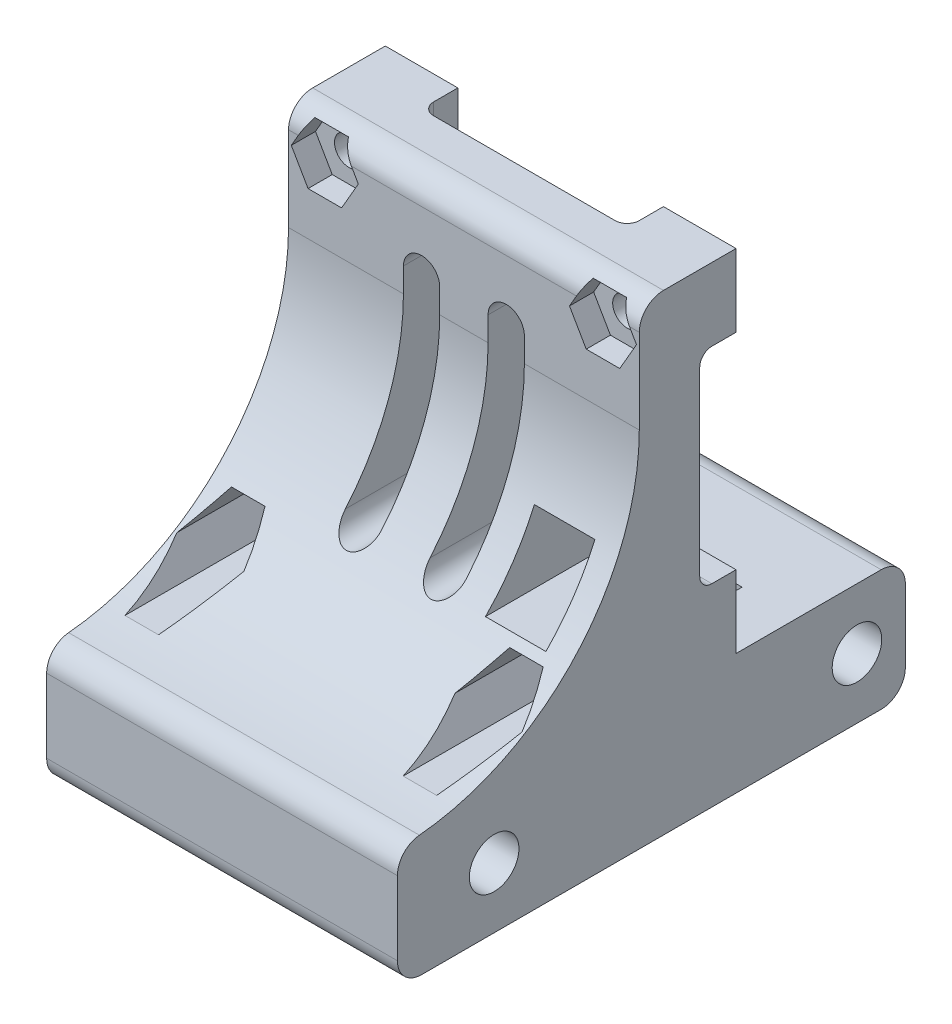
SolidWorks part; units mm, degrees
ref_plane "Front Plane" through (0, 0, 0) normal (0, 0, 1) x (1, 0, 0)
ref_plane "Top Plane" through (0, 0, 0) normal (0, 1, 0) x (1, 0, 0)
ref_plane "Right Plane" through (0, 0, 0) normal (1, 0, 0) x (0, 0, -1)
sketch "Sketch3" plane through (0, 0, 0) normal (0, 0, 1) x (1, 0, 0)
  line L0 (14.5, 29) -> (14.5, 0) construction
  line L1 (0, 0) -> (29, 0)
  line L2 (0, 0) -> (0, 29)
  line L3 (0, 29) -> (29, 29)
  line L4 (29, 0) -> (29, 29)
  line L5 (0, 14.5) -> (29, 14.5) construction
  line L6 (18, 7) -> (18, 22) construction
  line L7 (27, 12) -> (22, 12)
  line L8 (27, 12) -> (27, 6)
  line L9 (27, 6) -> (22, 6)
  line L10 (22, 12) -> (22, 6)
  line L11 (16.5, 7) -> (16.5, 22)
  line L12 (19.5, 7) -> (19.5, 22)
  line L13 (11, 7) -> (11, 22) construction
  line L14 (12.5, 7) -> (12.5, 22)
  line L15 (9.5, 7) -> (9.5, 22)
  circle A0 centre (3, 26) radius 1.2
  circle A1 centre (26, 26) radius 1.2
  circle A2 centre (26, 3) radius 1.2
  circle A3 centre (3, 3) radius 1.2
  arc A4 (16.5, 7) -> (19.5, 7) centre (18, 7) ccw
  arc A5 (19.5, 22) -> (16.5, 22) centre (18, 22) ccw
  arc A6 (12.5, 7) -> (9.5, 7) centre (11, 7) cw
  arc A7 (9.5, 22) -> (12.5, 22) centre (11, 22) cw
  point P23 (18, 14.5)
  point P31 (11, 14.5)
  dimension "D3" = 2.4
  dimension "D1" = 29
  dimension "D2" = 29
  dimension "D4" = 11.5
  dimension "D5" = 11.5
  dimension "D6" = 2
  dimension "D7" = 6
  dimension "D8" = 6
  dimension "D9" = 5
  dimension "D10" = 15
  dimension "D11" = 3
  dimension "D12" = 3.5
extrude "Boss-Extrude1" add sketch "Sketch3" along normal blind 5
sketch "Sketch4" plane through (0, 0, 0) normal (0, 1, 0) x (1, 0, 0)
  line L0 (29, -5) -> (29, 0) construction
  line L1 (0, 17) -> (29, 17)
  line L2 (0, 17) -> (0, -25)
  line L3 (0, -25) -> (29, -25)
  line L4 (29, 17) -> (29, -25)
  line L5 (0, -5) -> (0, 0) construction
  line L6 (0, -5) -> (29, -5) construction
  line L7 (0, 0) -> (29, 0) construction
  line L8 (24.5, -3) -> (4.5, -3)
  line L9 (24.5, -3) -> (24.5, 8)
  line L10 (24.5, 8) -> (4.5, 8)
  line L11 (4.5, -3) -> (4.5, 8)
  line L12 (14.5, 0) -> (14.5, -6) construction
  point P18 (14.5, -3)
  dimension "D1" = 42
  dimension "D2" = 20
  dimension "D3" = 20
  dimension "D4" = 11
  dimension "D5" = 3
extrude "Boss-Extrude2" add sketch "Sketch4" against normal blind 10 contours L2 L3 L4 L1 | L9 L8 L11 L10
sketch "Sketch5" plane through (0, 0, 0) normal (0, 0, -1) x (-1, 0, 0)
  line L0 (-14.5, 29) -> (-14.5, 14.5) construction
  line L1 (-29, 0) -> (-23, 0)
  line L2 (-29, 0) -> (-29, 6)
  line L3 (-29, 6) -> (-23, 6)
  line L4 (-23, 0) -> (-23, 6)
  line L5 (-29, 29) -> (0, 29) construction
  line L7 (-29, 14.5) -> (0, 14.5) construction
  line L8 (-29, 0) -> (-29, 29) construction
  line L9 (0, 29) -> (0, 0) construction
  line L10 (-29, 23) -> (-23, 23)
  line L11 (-23, 29) -> (-23, 23)
  line L12 (-29, 29) -> (-23, 29)
  line L13 (-29, 29) -> (-29, 23)
  line L14 (0, 6) -> (-6, 6)
  line L15 (-6, 0) -> (-6, 6)
  line L16 (0, 0) -> (-6, 0)
  line L17 (0, 0) -> (0, 6)
  line L18 (0, 29) -> (0, 23)
  line L19 (0, 29) -> (-6, 29)
  line L20 (-6, 29) -> (-6, 23)
  line L21 (0, 23) -> (-6, 23)
  circle A0 centre (-26, 3) radius 1.2 construction
  circle A1 centre (-3, 3) radius 1.2 construction
  circle A2 centre (-3, 26) radius 1.2 construction
  circle A3 centre (-26, 26) radius 1.2 construction
  circle A4 centre (-26, 3) radius 1.2
  circle A5 centre (-3, 3) radius 1.2
  circle A6 centre (-3, 26) radius 1.2
  circle A7 centre (-26, 26) radius 1.2
  dimension "D1" = 6
  dimension "D2" = 6
extrude "Boss-Extrude3" add sketch "Sketch5" along normal blind 3
fillet "Fillet1" radius 20 1 edges at (14.5, 0, 5)
sketch "Sketch6" plane through (0, 0, 5) normal (0, 0, 1) x (1, 0, 0)
  line L1 (4.3856, 0.6) -> (5.7713, 3)
  line L2 (5.7713, 3) -> (4.3856, 5.4)
  line L3 (4.3856, 5.4) -> (1.6144, 5.4)
  line L4 (1.6144, 5.4) -> (0.2287, 3)
  line L5 (0.2287, 3) -> (1.6144, 0.6)
  line L6 (1.6144, 0.6) -> (4.3856, 0.6)
  line L7 (24.6144, 0.6) -> (27.3856, 0.6)
  line L8 (27.3856, 0.6) -> (28.7713, 3)
  line L9 (28.7713, 3) -> (27.3856, 5.4)
  line L10 (27.3856, 5.4) -> (24.6144, 5.4)
  line L11 (24.6144, 5.4) -> (23.2287, 3)
  line L12 (23.2287, 3) -> (24.6144, 0.6)
  line L13 (4.3856, 23.6) -> (5.7713, 26)
  line L14 (5.7713, 26) -> (4.3856, 28.4)
  line L15 (4.3856, 28.4) -> (1.6144, 28.4)
  line L16 (1.6144, 28.4) -> (0.2287, 26)
  line L17 (0.2287, 26) -> (1.6144, 23.6)
  line L18 (1.6144, 23.6) -> (4.3856, 23.6)
  line L19 (27.3856, 23.6) -> (28.7713, 26)
  line L20 (28.7713, 26) -> (27.3856, 28.4)
  line L21 (27.3856, 28.4) -> (24.6144, 28.4)
  line L22 (24.6144, 28.4) -> (23.2287, 26)
  line L23 (23.2287, 26) -> (24.6144, 23.6)
  line L24 (24.6144, 23.6) -> (27.3856, 23.6)
  circle A2 centre (3, 3) radius 2.4 construction
  circle A3 centre (26, 3) radius 2.4 construction
  circle A4 centre (3, 26) radius 2.4 construction
  circle A5 centre (26, 26) radius 2.4 construction
  point P28 (3, 28.4)
  dimension "D1" = 4.8
  dimension "D2" = 4.8
  dimension "D3" = 4.8
  dimension "D4" = 4.8
extrude "Cut-Extrude1" cut sketch "Sketch6" along normal through all and the other way blind 2
fillet "Fillet2" radius 1 8 edges at (28, 6, 0) (26, 23, 0) (3, 23, 0) (3, 6, 0) (6, 3, 0) (6, 26, 0) (23, 26, 0) (23, 3, 0)
sketch "Sketch7" plane through (0, 0, 0) normal (-1, 0, 0) x (0, 0, 1)
  line L0 (-17, 0) -> (-17, -10) construction
  line L1 (-17, -5) -> (25, -5) construction
  line L2 (25, -10) -> (25, 0) construction
  line L3 (4, -10) -> (4, -5) construction
  line L4 (-17, -10) -> (25, -10) construction
  circle A0 centre (-13, -5) radius 2.05
  circle A1 centre (17, -5) radius 2.05
  dimension "D1" = 4.1
  dimension "D2" = 4.1
  dimension "D3" = 30
  dimension "D4" = 17
extrude "Cut-Extrude2" cut sketch "Sketch7" against normal through all
fillet "Fillet3" radius 2 5 edges at (14.5, -10, -17) (14.5, 0, -17) (14.5, 29, 5) (14.5, -10, 25) (14.5, 0, 25)
